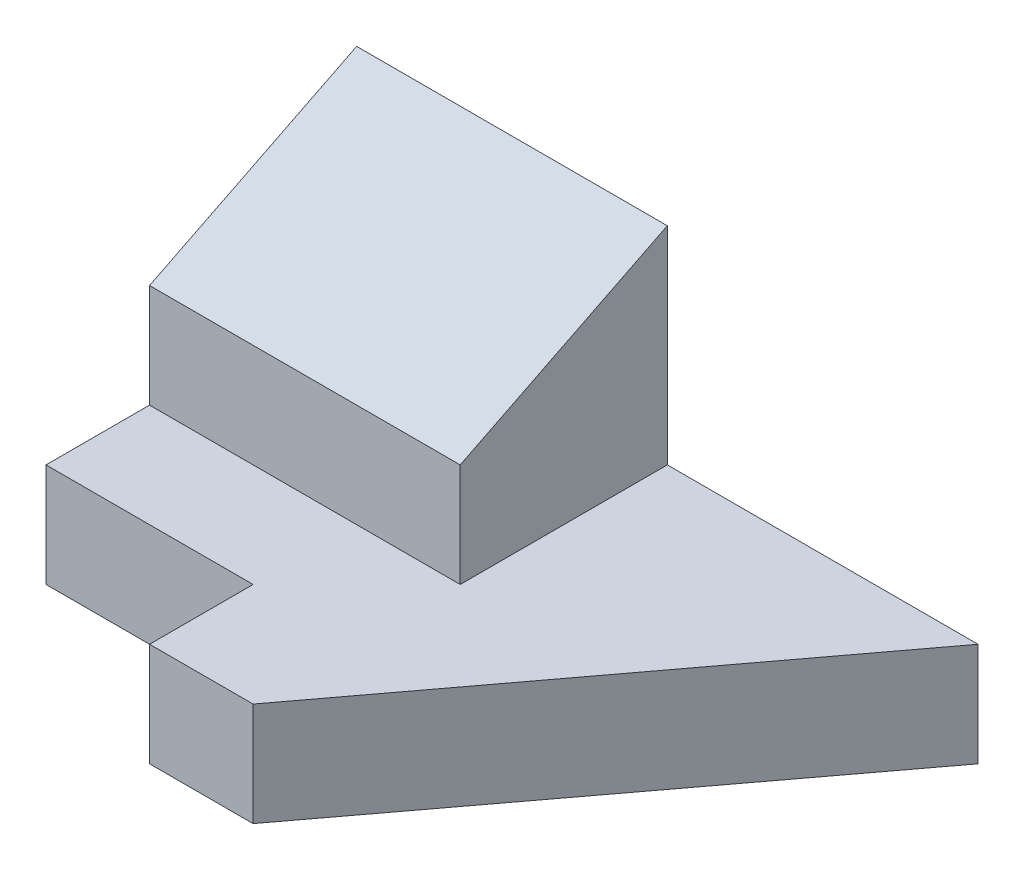
SolidWorks part; units mm, degrees
ref_plane "前基準面" through (0, 0, 0) normal (0, 0, 1) x (1, 0, 0)
ref_plane "上基準面" through (0, 0, 0) normal (0, 1, 0) x (1, 0, 0)
ref_plane "右基準面" through (0, 0, 0) normal (1, 0, 0) x (0, 0, -1)
sketch "草圖1" plane through (0, 0, 0) normal (0, 1, 0) x (1, 0, 0)
  line L0 (0, -10) -> (15, 10)
  line L1 (-5, -10) -> (0, -10)
  line L2 (-15, -5) -> (-15, 10)
  line L3 (-15, 10) -> (15, 10)
  line L5 (-15, -10) -> (15, 10) construction
  line L6 (-15, 10) -> (5, -3.3333) construction
  line L9 (-15, -5) -> (-5, -5)
  line L10 (-5, -10) -> (-5, -5)
  line L11 (-15, 10) -> (0, 10)
  line L12 (-15, 10) -> (-15, 0)
  line L13 (-15, 0) -> (0, 0)
  line L14 (0, 10) -> (0, 0)
  point P0 (0, 0)
  dimension "D1" = 20
  dimension "D4" = 5
  dimension "D5" = 10
  dimension "D6" = 15
  dimension "D7" = 10
extrude "填料-伸長1" add sketch "草圖1" along normal blind 5 contours L3 L14 L13 L2 L9 L10 L1 L0 | L14 L3 L2 L13 region at (0.5, 0, -0.5) region at (-7.5, 0, -5)
extrude "填料-伸長2" add sketch "草圖1<3>" along normal blind 15 contours L14 L3 L2 L13 region at (-7.5, 0, -5)
sketch "草圖1<3>" plane through (0, 0, 0) normal (0, 1, 0) x (1, 0, 0) same geometry as "草圖1"
sketch "草圖2" plane through (0, 0, 0) normal (1, 0, 0) x (0, 0, -1)
  line L0 (10, 15) -> (0, 10)
  line L1 (0, 15) -> (0, 5) construction
  line L2 (0, 10) -> (0, 15)
  line L3 (0, 15) -> (10, 15)
  dimension "D1" = 5
extrude "除料-伸長1" cut sketch "草圖2" against normal blind 15
